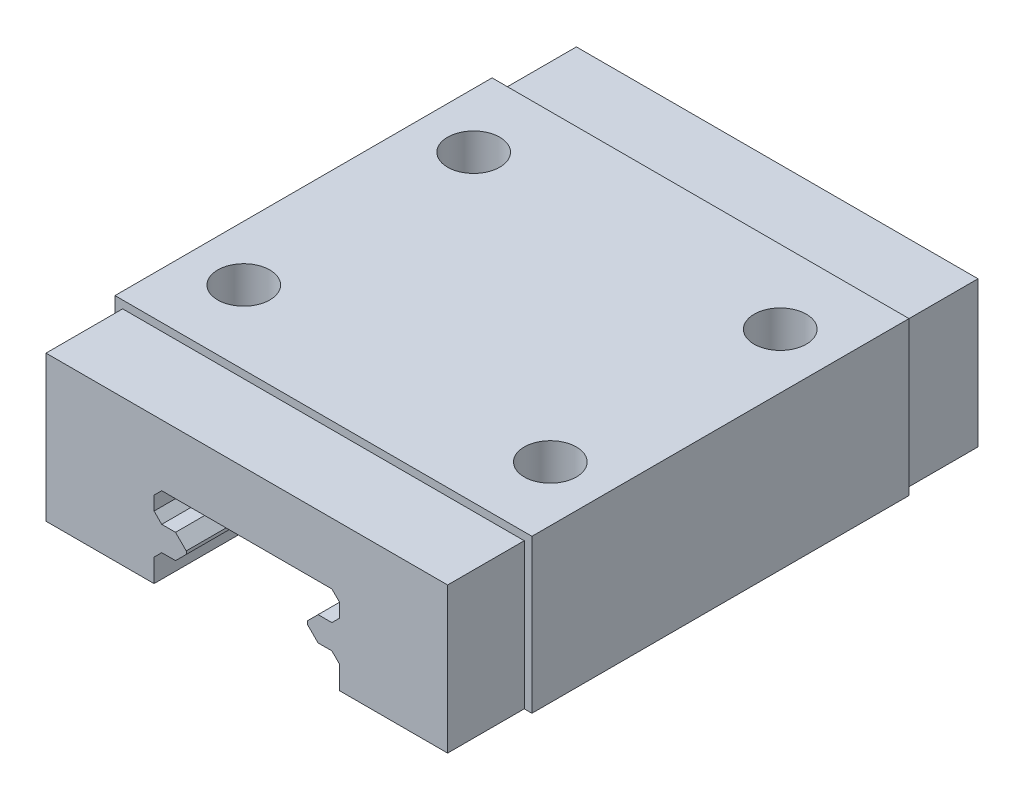
SolidWorks part; units mm, degrees
ref_plane "Front Plane" through (0, 0, 0) normal (0, 0, 1) x (1, 0, 0)
ref_plane "Top Plane" through (0, 0, 0) normal (0, 1, 0) x (1, 0, 0)
ref_plane "Right Plane" through (0, 0, 0) normal (1, 0, 0) x (0, 0, -1)
sketch "Sketch1" plane through (0, 0, 0) normal (0, 0, 1) x (1, 0, 0)
  line L1 (-13.6, 5) -> (13.6, 5)
  line L2 (-13.6, 5) -> (-13.6, -5)
  line L3 (-13.6, -5) -> (13.6, -5)
  line L4 (13.6, 5) -> (13.6, -5)
  line L5 (-13.6, 5) -> (13.6, -5) construction
  line L6 (-13.6, -5) -> (13.6, 5) construction
  point P0 (0, 0)
  dimension "D1" = 10
  dimension "D2" = 27.2
extrude "Boss-Extrude1" add sketch "Sketch1" along normal blind 34.6
sketch "Sketch2" plane through (0, 0, 34.6) normal (0, 0, 1) x (1, 0, 0)
  line L0 (-6.05, -3.5) -> (-6.05, -7)
  line L4 (6.05, -7) -> (6.05, -3.5)
  line L5 (6.05, -3.5) -> (5.55, -3)
  line L6 (5.55, -3) -> (3.95, -3)
  line L7 (3.95, -3) -> (3.95, -1.4)
  line L8 (3.95, -1.4) -> (5.55, -1.4)
  line L9 (5.55, -1.4) -> (6.05, -0.9)
  line L10 (6.05, -0.9) -> (6.05, 0)
  line L11 (6.05, 0) -> (5.55, 0.5)
  line L12 (5.55, 0.5) -> (-5.55, 0.5)
  line L13 (-5.55, 0.5) -> (-6.05, 0)
  line L14 (-6.05, 0) -> (-6.05, -0.9)
  line L15 (-6.05, -0.9) -> (-5.55, -1.4)
  line L16 (-5.55, -1.4) -> (-3.95, -1.4)
  line L17 (-3.95, -1.4) -> (-3.95, -3)
  line L18 (-3.95, -3) -> (-5.55, -3)
  line L19 (-5.55, -3) -> (-6.05, -3.5)
  line L20 (-13.6, -5) -> (13.6, -5) construction
  point P2 (0, 0.5)
  line M24 (-13.6, -5) -> (13.6, -5)
  dimension "D1" = 5.5
extrude "Cut-Extrude1" cut sketch "Sketch2" against normal blind 34.6 and the other way through all contours L18 L19 L0 L4 L5 L6 L7 L8 L9 L10 L11 L12 L13 L14 L15 L16 L17 M24 region at (0, -2.267, 34.6)
chamfer "Chamfer1" distance 0.7 angle 45 4 edges at (-3.95, -3, 17.3) (-3.95, -1.4, 17.3) (3.95, -3, 17.3) (3.95, -1.4, 17.3)
sketch "Sketch5" plane through (0, 5, 0) normal (0, 1, 0) x (1, 0, 0)
  point P0 (0, -17.3)
hole_wizard "M3 Clearance Hole1" positions "Sketch3" profile "Sketch4" hole size "M3" standard "ISO"
sketch "Sketch3" plane through (0, 5, 0) normal (0, 1, 0) x (1, 0, 0)
  point P0 (-10, -24.8)
  point P2 (-10, -9.8)
  point P4 (10, -9.8)
  point P6 (10, -24.8)
  dimension "D1" = 7.5
  dimension "D2" = 7.5
  dimension "D3" = 7.5
  dimension "D4" = 7.5
  dimension "D5" = 10
  dimension "D6" = 10
  dimension "D7" = 10
  dimension "D8" = 10
sketch "Sketch4" plane through (-10, 5, 24.8) normal (1, 0, 0) x (0, 0, 1)
  line L0 (0, 0) -> (0, 6.0215)
  line L1 (0, 6.0215) -> (1.7, 5)
  line L2 (1.7, 5) -> (1.7, 0)
  line L5 (1.7, 0) -> (0, 0)
  line L10 (0, 6.0215) -> (-1.7, 5) construction
  line L11 (0, -6.35) -> (0, 107.95) construction
  dimension "Hole Dia." = 3.4
  dimension "Hole Depth" = 5
  dimension "Drill Angle" = 118
sketch "Sketch6" plane through (0, 5, 0) normal (0, 1, 0) x (1, 0, 0)
  circle A0 centre (10, -24.8) radius 1.7 construction
  circle A1 centre (10, -9.8) radius 1.7 construction
  circle A2 centre (-10, -9.8) radius 1.7 construction
  circle A3 centre (-10, -24.8) radius 1.7 construction
  circle A4 centre (10, -24.8) radius 1.7
  circle A5 centre (10, -9.8) radius 1.7
  circle A6 centre (-10, -9.8) radius 1.7
  circle A7 centre (-10, -24.8) radius 1.7
  point P16 (0, -17.3)
sketch "Sketch7" plane through (0, 5, 0) normal (0, 1, 0) x (1, 0, 0)
  line L0 (-13.6, -29.6) -> (13.6, -29.6)
  line L1 (-13.6, -34.6) -> (-13.6, 0) construction
  line L2 (13.6, -34.6) -> (13.6, 0) construction
  line L3 (13.6, -34.6) -> (-13.6, -34.6) construction
  line L4 (-13.6, -5) -> (13.6, -5)
  line L5 (13.6, 0) -> (-13.6, 0) construction
  line L10 (13.6, 0) -> (-13.6, 0)
  line L11 (-13.6, 0) -> (-13.6, -34.6)
  line L12 (-13.6, -34.6) -> (13.6, -34.6)
  line L13 (13.6, -34.6) -> (13.6, 0)
  line L14 (13.6, 0) -> (-13.6, 0)
  line L15 (-13.6, 0) -> (-13.6, -34.6)
  line L16 (-13.6, -34.6) -> (13.6, -34.6)
  line L17 (13.6, -34.6) -> (13.6, 0)
  line M11 (13.6, 0) -> (-13.6, 0)
  line M12 (-13.6, 0) -> (-13.6, -34.6)
  line M13 (-13.6, -34.6) -> (13.6, -34.6)
  line M14 (13.6, -34.6) -> (13.6, 0)
  dimension "D1" = 5
  dimension "D2" = 5
  dimension "D3" = 0
extrude "Cut-Extrude2" cut sketch "Sketch7" against normal blind 0.5 contours L0 M12 M13 M14 | L4 M12 M14 M11 region at (0, 5, 32.1) region at (0, 5, 2.5)
sketch "Sketch8" plane through (13.6, 0, 0) normal (1, 0, 0) x (0, 0, -1)
  line L0 (-29.6, 4.5) -> (-29.6, -5)
  line L1 (-34.6, -5) -> (0, -5) construction
  line L2 (-5, 4.5) -> (-5, -5)
  line L11 (-29.6, 5) -> (-29.6, 4.5)
  line L12 (-29.6, 4.5) -> (-34.6, 4.5)
  line L13 (-34.6, 4.5) -> (-34.6, -5)
  line L14 (-34.6, -5) -> (0, -5)
  line L15 (0, -5) -> (0, 4.5)
  line L16 (0, 4.5) -> (-5, 4.5)
  line L17 (-5, 4.5) -> (-5, 5)
  line L18 (-5, 5) -> (-29.6, 5)
  line L19 (-29.6, 5) -> (-29.6, 4.5)
  line L20 (-29.6, 4.5) -> (-34.6, 4.5)
  line L21 (-34.6, 4.5) -> (-34.6, -5)
  line L22 (-34.6, -5) -> (0, -5)
  line L23 (0, -5) -> (0, 4.5)
  line L24 (0, 4.5) -> (-5, 4.5)
  line L25 (-5, 4.5) -> (-5, 5)
  line L26 (-5, 5) -> (-29.6, 5)
  line M10 (-29.6, 4.5) -> (-34.6, 4.5)
  line M11 (-34.6, 4.5) -> (-34.6, -5)
  line M12 (-34.6, -5) -> (0, -5)
  line M13 (0, -5) -> (0, 4.5)
  line M14 (0, 4.5) -> (-5, 4.5)
  dimension "D1" = 0
extrude "Cut-Extrude3" cut sketch "Sketch8" against normal blind 0.5 contours L0 M10 M11 M12 | L2 M14 M12 M13 region at (13.6, -0.25, 32.1) region at (13.6, -0.25, 2.5)
mirror "Mirror1" about plane through (0, 0, 0) normal (1, 0, 0) of "Cut-Extrude3"
